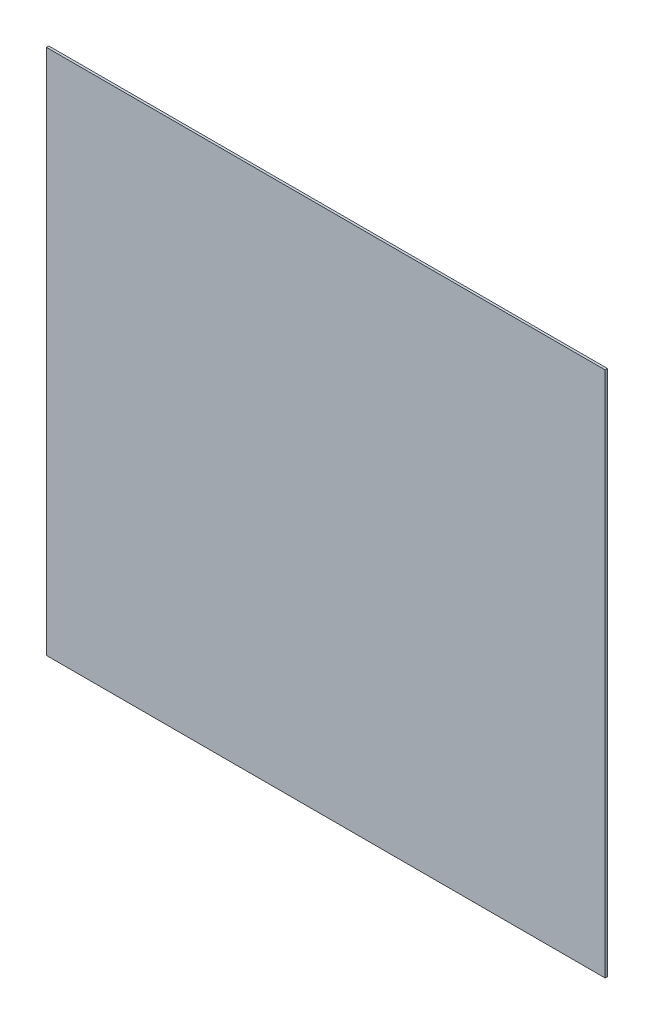
SolidWorks part; units mm, degrees
material "AISI 4130 Steel, normalized at 870C"
ref_plane "Front Plane" through (0, 0, 0) normal (0, 0, 1) x (1, 0, 0)
ref_plane "Top Plane" through (0, 0, 0) normal (0, 1, 0) x (1, 0, 0)
ref_plane "Right Plane" through (0, 0, 0) normal (1, 0, 0) x (0, 0, -1)
sketch "Sketch2" plane through (0, 0, 0) normal (0, 0, 1) x (1, 0, 0)
  line L1 (-175, 165) -> (175, 165)
  line L2 (-175, 165) -> (-175, -165)
  line L3 (-175, -165) -> (175, -165)
  line L4 (175, 165) -> (175, -165)
  dimension "D1" = 350
  dimension "D2" = 330
  dimension "D3" = 165
  dimension "D4" = 175
extrude "Boss-Extrude2" add sketch "Sketch2" along normal blind 1.5
